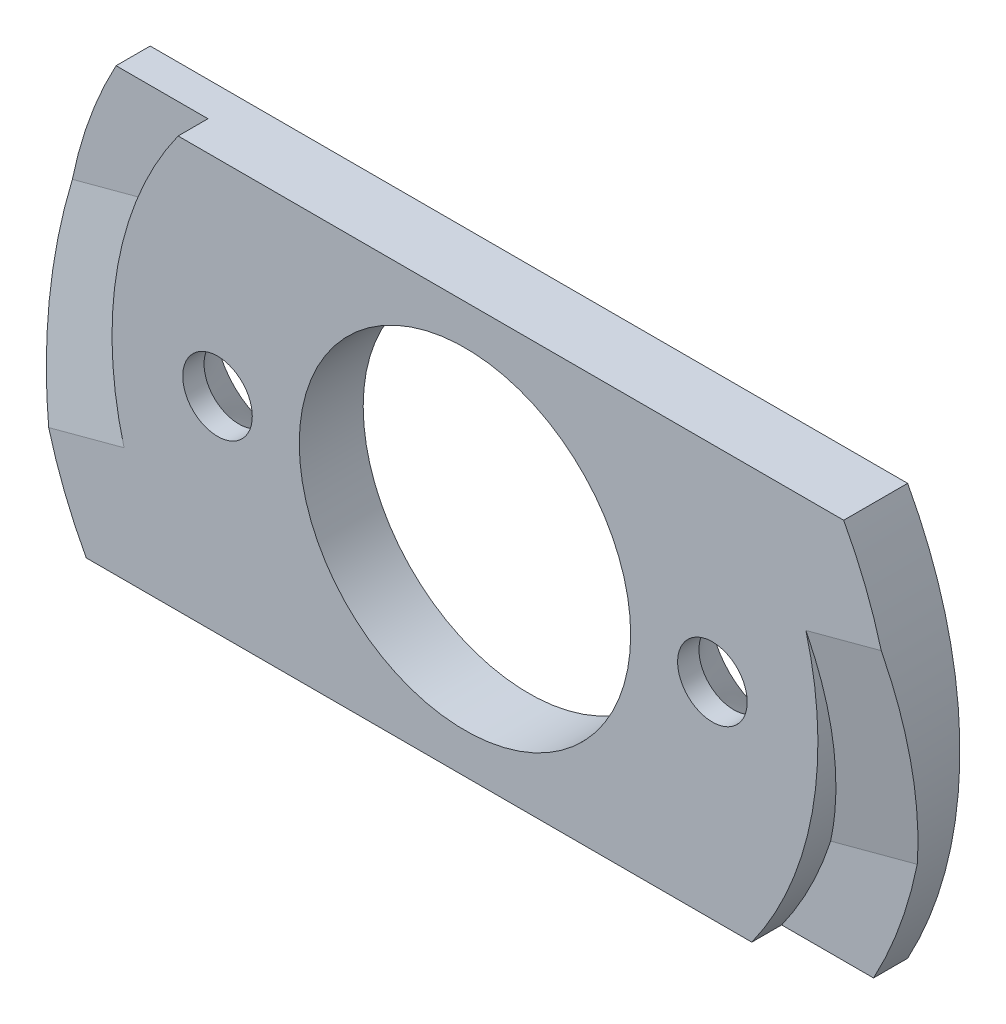
SolidWorks part; units mm, degrees
ref_plane "Front Plane" through (0, 0, 0) normal (0, 0, 1) x (1, 0, 0)
ref_plane "Top Plane" through (0, 0, 0) normal (0, 1, 0) x (1, 0, 0)
ref_plane "Right Plane" through (0, 0, 0) normal (1, 0, 0) x (0, 0, -1)
sketch "Sketch1" plane through (0, 0, 0) normal (0, 0, 1) x (1, 0, 0)
  line L0 (0, 9.65) -> (0, -9.65) construction
  line L5 (-19.531, -5.2333) -> (19.531, 5.2333)
  line L6 (-17.7687, -9.65) -> (17.7687, -9.65)
  line L11 (-20.22, 0) -> (20.22, 0) construction
  line L12 (-17.7687, 9.65) -> (17.7687, 9.65)
  circle A2 centre (-11.61, 0) radius 1.6319
  circle A3 centre (11.61, 0) radius 1.6319
  circle A4 centre (0, 0) radius 7.775
  arc A5 (-17.7687, 9.65) -> (-17.7687, -9.65) centre (0, 0) ccw
  arc A6 (-13.4578, 9.65) -> (-13.4578, -9.65) centre (0, 0) ccw
  arc A7 (17.7687, -9.65) -> (17.7687, 9.65) centre (0, 0) ccw
  arc A8 (13.4578, -9.65) -> (13.4578, 9.65) centre (0, 0) ccw
  dimension "D1" = 20.22
  dimension "D2" = 16.56
  dimension "D3" = 15.55
  dimension "D5" = 3.2639
  dimension "D6" = 15
  dimension "D4" = 23.22
  dimension "D9" = 19.3
extrude "Boss-Extrude1" add sketch "Sketch1" along normal blind 3 contours L6 A8 L12 A6 A2 A3 A4 | L5 A8 L12 A6 A4 A2 | A6 L5 A5 L6 | A8 L5 A7 L12 region at (-16.7509, -7.2494, 0) region at (-15.9436, 2.9036, 0) region at (-11.6612, -3.4912, 0) region at (16.7509, 7.2494, 0)
extrude "Boss-Extrude2" add sketch "Sketch1<3>" along normal blind 1.6 contours L11 A5 L6 A6 | A5 L11 A6 L12 | L11 A8 L6 A7 | A8 L11 A7 L12 region at (-17.7085, 2.5897, 0) region at (-16.7509, -7.2494, 0) region at (16.7509, 7.2494, 0) region at (17.7085, -2.5897, 0)
sketch "Sketch1<3>" plane through (0, 0, 0) normal (0, 0, 1) x (1, 0, 0) same geometry as "Sketch1"
chamfer "Chamfer1" distance 2 distance2 1.5 2 edges at (13.2419, 0, 0) (-9.9781, 0, 0) first distance on face at (13.2419, 0, 3) first distance on face at (-9.9781, 0, 3)
chamfer "Chamfer2" distance 1.4 distance2 9 1 edges at (-17.7634, -4.7597, 1.6) first distance on face at (-17.7634, -4.7597, 2.3)
chamfer "Chamfer3" distance 9 distance2 1.4 1 edges at (17.7634, 4.7597, 1.6) first distance on face at (17.4371, -2.5588, 1.6)
